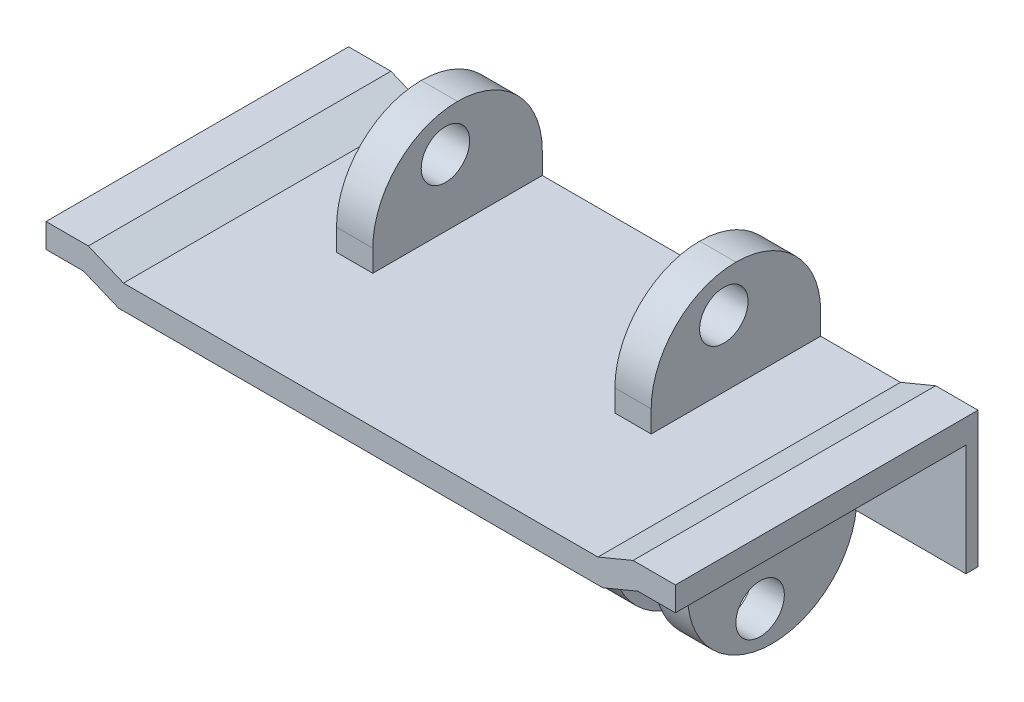
SolidWorks part; units mm, degrees
ref_plane "Front Plane" through (0, 0, 0) normal (0, 0, 1) x (1, 0, 0)
ref_plane "Top Plane" through (0, 0, 0) normal (0, 1, 0) x (1, 0, 0)
ref_plane "Right Plane" through (0, 0, 0) normal (1, 0, 0) x (0, 0, -1)
sketch "Sketch2" plane through (0, 0, 0) normal (0, 0, 1) x (1, 0, 0)
  line L0 (-5, 6) -> (-10, 6)
  line L1 (-5, 6) -> (5, 6) construction
  line L2 (-5, 6) -> (-5, -9) construction
  line L4 (5, 6) -> (5, -9) construction
  line L7 (-10, 6) -> (-10, -9)
  line L8 (-10, -9) -> (-5, -9)
  line L9 (-5, -9) -> (-5, 6)
  line L10 (0, 6) -> (0, -6) construction
  line L11 (10, -9) -> (5, -9)
  line L12 (10, 6) -> (10, -9)
  line L13 (5, 6) -> (10, 6)
  line L14 (5, -9) -> (5, 6)
  point P0 (0, 0)
  point P11 (0, 0)
  point P16 (0, 6)
  dimension "D1" = 15
  dimension "D2" = 10
  dimension "D3" = 5
extrude "Boss-Extrude1" add sketch "Sketch2" along normal blind 14
sketch "Sketch4" plane through (0, 0, 0) normal (0, 0, 1) x (1, 0, 0)
  line L0 (0, 0) -> (0, 50000) construction
  line L1 (-6.1796, 6) -> (49993.8204, 6) construction
  line L2 (-10, 6) -> (-20, 6)
  line L3 (10, 6) -> (20, 6)
  line L4 (-20, 6) -> (-22.9016, 7.2064)
  line L5 (-22.9016, 7.2064) -> (-26, 7.2064)
  line L6 (-10, 8) -> (-19.6008, 8)
  line L7 (-19.6008, 8) -> (-22.5024, 9.2064)
  line L8 (-22.5024, 9.2064) -> (-26, 9.2064)
  line L9 (-26, 9.2064) -> (-26, 7.2064)
  line L10 (-10, 6) -> (10, 6)
  line L11 (-10, 8) -> (10, 8)
  line L12 (10, 8) -> (19.6008, 8)
  line L13 (19.6008, 8) -> (22.5024, 9.2064)
  line L14 (20, 6) -> (22.9016, 7.2064)
  line L15 (22.9016, 7.2064) -> (26, 7.2064)
  line L16 (26, 9.2064) -> (26, 7.2064)
  line L17 (22.5024, 9.2064) -> (26, 9.2064)
  point P19 (0, 6)
  point P20 (0, 8)
  dimension "D1" = 10
  dimension "D3" = 6
  dimension "D2" = 2
extrude "Boss-Extrude3" add sketch "Sketch4" along normal blind 25
sketch "Sketch9" plane through (0, 0, 14) normal (0, 0, 1) x (1, 0, 0)
  line L0 (-10, -9) -> (-5, -9) construction
  line L1 (-5, 6) -> (-7.5, 6)
  line L2 (-5, 6) -> (-5, -9)
  line L3 (-5, -9) -> (-7.5, -9)
  line L4 (-7.5, 6) -> (-7.5, -9)
  line L5 (0, 7.972) -> (0, -7.972) construction
  line L6 (5, -9) -> (7.5, -9)
  line L7 (7.5, 6) -> (7.5, -9)
  line L8 (5, 6) -> (7.5, 6)
  line L9 (5, 6) -> (5, -9)
  point P11 (0, 0)
  dimension "D1" = 2.5
extrude "Cut-Extrude1" [suppressed] cut sketch "Sketch9" against normal blind 10
sketch "Sketch5" plane through (0, 0, 0) normal (0, 0, 1) x (1, 0, 0)
  line L0 (-10, 4.6) -> (-10, 50004.6) construction
  line L1 (0, 0) -> (0, 50000) construction
  line L2 (-10, 8) -> (-10, 16.8)
  line L3 (19.6008, 8) -> (-19.6008, 8) construction
  line L4 (-10, 16.8) -> (-13, 16.8)
  line L5 (-13, 16.8) -> (-13, 8)
  line L6 (-13, 8) -> (-10, 8)
  line L7 (13, 8) -> (10, 8)
  line L8 (13, 16.8) -> (13, 8)
  line L9 (10, 16.8) -> (13, 16.8)
  line L10 (10, 8) -> (10, 16.8)
  dimension "D1" = 3
  dimension "D2" = 8.8
extrude "Boss-Extrude4" add sketch "Sketch5" along normal blind 14
sketch "Sketch7" plane through (0, 0, 0) normal (0, 0, 1) x (1, 0, 0)
  line L0 (-13, 5.6) -> (-13, -49994.4) construction
  line L1 (-19.6008, 5.6) -> (-19.6008, -49994.4) construction
  line L2 (-10.0004, -9) -> (49989.9996, -9) construction
  line L3 (-15.0004, 6) -> (-50015.0004, 6) construction
  line L4 (-16, 6) -> (-16, -9)
  line L5 (-16, -9) -> (-13, -9)
  line L6 (-13, -9) -> (-13, 6)
  line L7 (-13, 6) -> (-16, 6)
  line L8 (0, 0) -> (0, -50000) construction
  line L13 (0, -13.75) -> (0, 13.75) construction
  line L14 (13, -9) -> (13, 6)
  line L15 (16, -9) -> (13, -9)
  line L16 (16, 6) -> (16, -9)
  line L17 (13, 6) -> (16, 6)
  dimension "D1" = 3
extrude "Boss-Extrude5" add sketch "Sketch7" along normal blind 14
sketch "Sketch15" plane through (0, -9, 0) normal (0, -1, 0) x (1, 0, 0)
  line L16 (-10, 14) -> (-9.7, 14)
  line L17 (-10, 14) -> (-5, 14) construction
  line L18 (-10, 14) -> (-10, 0) construction
  line L19 (-9.7, 14) -> (-9.7, 0)
  line L20 (-10, 0) -> (-5, 0) construction
  line L21 (-9.7, 0) -> (-10, 0)
  line L22 (-10, 0) -> (-10, 14)
  line L23 (0, -13.75) -> (0, 13.75) construction
  line L24 (9.7, 0) -> (10, 0)
  line L25 (9.7, 14) -> (9.7, 0)
  line L26 (10, 14) -> (9.7, 14)
  line L27 (10, 0) -> (10, 14)
  line L28 (-13, 14) -> (-13.3, 14)
  line L29 (-16, 14) -> (-13, 14) construction
  line L30 (-13.3, 14) -> (-13.3, 0)
  line L31 (-16, 0) -> (-13, 0) construction
  line L32 (-13.3, 0) -> (-13, 0)
  line L33 (-13, 0) -> (-13, 14)
  line L34 (13.3, 0) -> (13, 0)
  line L35 (13.3, 14) -> (13.3, 0)
  line L36 (13, 14) -> (13.3, 14)
  line L37 (13, 0) -> (13, 14)
  dimension "D1" = 0.3
  dimension "D2" = 0.3
extrude "Cut-Extrude2" cut sketch "Sketch15" against normal up to surface (15 mm away) up to face at (0, 6, 8.1)
sketch "Sketch16" plane through (0, -9, 0) normal (0, -1, 0) x (1, 0, 0)
  line L0 (-5, 14) -> (-5.15, 14)
  line L1 (-9.7, 14) -> (-5, 14) construction
  line L2 (-5.15, 14) -> (-5.15, 0)
  line L3 (-9.7, 0) -> (-5, 0) construction
  line L4 (-5.15, 0) -> (-5, 0)
  line L5 (-5, 0) -> (-5, 14)
  line L6 (0, -13.75) -> (0, 13.75) construction
  line L7 (5.15, 0) -> (5, 0)
  line L8 (5.15, 14) -> (5.15, 0)
  line L9 (5, 14) -> (5.15, 14)
  line L10 (5, 0) -> (5, 14)
  dimension "D1" = 0.15
extrude "Cut-Extrude3" cut sketch "Sketch16" against normal up to surface (15 mm away) up to face at (0, 6, 8.1)
fillet "Fillet1" radius 7 8 edges at (7.425, -9, 0) (7.425, -9, 14) (-7.425, -9, 0) (-7.425, -9, 14) (-14.65, -9, 0) (-14.65, -9, 14) (14.65, -9, 0) (14.65, -9, 14)
hole_wizard "Ø4.0mm Dowel Hole2" positions "Sketch10" profile "Sketch11" hole size "Ø4.0" standard "ANSI Metric" end condition through all
sketch "Sketch10" plane through (16, 0, 0) normal (1, 0, 0) x (0, 0, -1)
  line L7 (-25, 6) -> (0, 6) construction
  line L9 (-14, -2) -> (-14, 6) construction
  point P0 (-8, -6)
  dimension "D1" = 6
  dimension "D2" = 12
sketch "Sketch11" plane through (16, -6, 8) normal (0, 1, 0) x (0, 0, -1)
  line L0 (0, 0) -> (0, 42)
  line L1 (0, 42) -> (2, 42)
  line L2 (2, 42) -> (2, 0)
  line L5 (2, 0) -> (0, 0)
  line L11 (0, -6.35) -> (0, 107.95) construction
  dimension "Thru Hole Dia." = 4
  dimension "Thru Hole Depth" = 42
fillet "Fillet2" radius 7 4 edges at (-11.5, 16.8, 0) (-11.5, 16.8, 14) (11.5, 16.8, 0) (11.5, 16.8, 14)
hole_wizard "Ø4.0mm Dowel Hole1" positions "Sketch12" profile "Sketch13" hole size "Ø4.0" standard "ANSI Metric"
sketch "Sketch12" plane through (13, 0, 0) normal (1, 0, 0) x (0, 0, -1)
  line L1 (-25, 8) -> (0, 8) construction
  line L2 (-25, 8) -> (0, 8)
  circle A8 centre (-8, -6) radius 2 construction
  circle A9 centre (-8, -6) radius 2
  point P10 (-8, 13.5)
  dimension "D1" = 5.5
sketch "Sketch13" plane through (13, 13.5, 8) normal (0, 1, 0) x (0, 0, -1)
  line L0 (0, 0) -> (0, 27.2017)
  line L1 (0, 27.2017) -> (2, 26)
  line L2 (2, 26) -> (2, 0)
  line L5 (2, 0) -> (0, 0)
  line L10 (0, 27.2017) -> (-2, 26) construction
  line L11 (0, -6.35) -> (0, 107.95) construction
  dimension "Hole Dia." = 4
  dimension "Hole Depth" = 26
  dimension "Drill Angle" = 118
sketch "Sketch14" plane through (0, 0, 0) normal (0, 0, 1) x (1, 0, 0)
  line L4 (0, 14.6739) -> (0, -14.6739) construction
  line L5 (-26, 7.2064) -> (-22.9016, 7.2064)
  line L6 (-26, 6) -> (-26, 7.2064)
  line L7 (-20, 6) -> (-26, 6)
  line L8 (-22.9016, 7.2064) -> (-20, 6)
  line L13 (-16, 6) -> (-20, 6)
  line L14 (-26, -2) -> (-26, 6)
  line L15 (-16, -2) -> (-26, -2)
  line L18 (-16, 6) -> (-16, -2)
  line L21 (16, 6) -> (16, -2)
  line L22 (16, -2) -> (26, -2)
  line L23 (26, -2) -> (26, 6)
  line L24 (16, 6) -> (20, 6)
  line L25 (22.9016, 7.2064) -> (20, 6)
  line L26 (20, 6) -> (26, 6)
  line L27 (26, 6) -> (26, 7.2064)
  line L28 (26, 7.2064) -> (22.9016, 7.2064)
  point P11 (0, 0)
extrude "Boss-Extrude6" add sketch "Sketch14" along normal blind 1 contours L8 L5 L6 L7 | L14 L13 L7 | L27 L28 L25 L26 | L26 L24 L21 L22 L23 region at (-23.6483, 6.5391, 0) region at (-21, 2, 0) region at (21, 2, 0) region at (23.6483, 6.5391, 0)
sketch "Sketch18" plane through (-5.15, 0, 0) normal (1, 0, 0) x (0, 0, -1)
  line L1 (-6.1109, -3.2351) -> (-9.4499, -2.9815)
  line L2 (-9.4499, -2.9815) -> (-11.339, -5.7464)
  line L3 (-11.339, -5.7464) -> (-9.8891, -8.7649)
  line L4 (-9.8891, -8.7649) -> (-6.5501, -9.0185)
  line L5 (-6.5501, -9.0185) -> (-4.661, -6.2536)
  line L6 (-4.661, -6.2536) -> (-6.1109, -3.2351)
  circle A0 centre (-8, -6) radius 2.9 construction
  dimension "D1" = 5.8
extrude "Cut-Extrude4" cut sketch "Sketch18" against normal blind 2.4
mirror "Mirror1" about plane through (0, 0, 0) normal (1, 0, 0) of "Cut-Extrude4"
